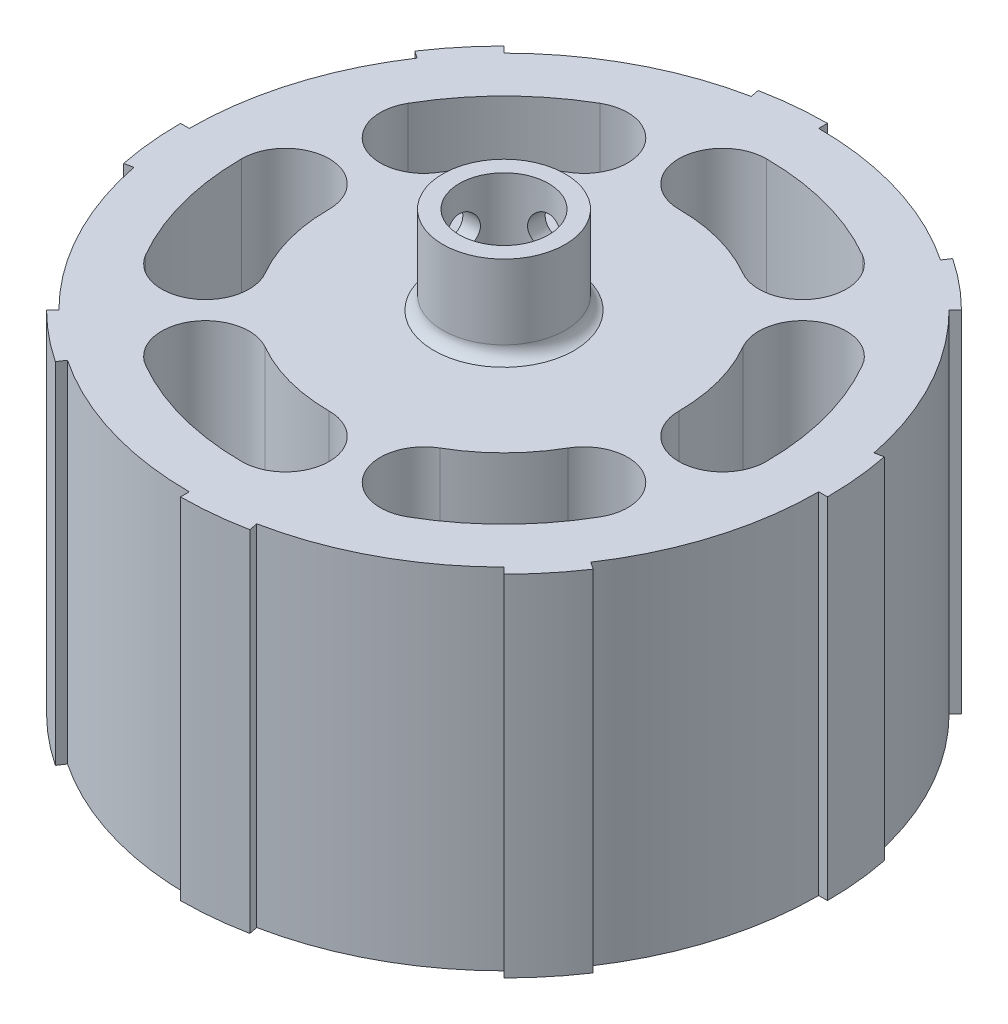
SolidWorks part; units mm, degrees
ref_plane "前视基准面" through (0, 0, 0) normal (0, 0, 1) x (1, 0, 0)
ref_plane "上视基准面" through (0, 0, 0) normal (0, 1, 0) x (1, 0, 0)
ref_plane "右视基准面" through (0, 0, 0) normal (1, 0, 0) x (0, 0, -1)
other "Configuration Table"
sketch "草图1" plane through (0, 0, 0) normal (0, 1, 0) x (1, 0, 0)
  circle A0 centre (0, 0) radius 37
  dimension "D1" = 74
extrude "凸台-拉伸1" add sketch "草图1" along normal blind 40
sketch "草图2" plane through (0, 40, 0) normal (0, 1, 0) x (1, 0, 0)
  circle A0 centre (0, 0) radius 5.1
  dimension "D1" = 10.2
extrude "切除-拉伸1" cut sketch "草图2" against normal blind 40
sketch "草图3" plane through (0, 40, 0) normal (0, 1, 0) x (1, 0, 0)
  line L0 (-1000, 0) -> (49000, 0) construction
  line L1 (0, -1000) -> (0, 49000) construction
  circle A0 centre (0, 0) radius 30
  circle A1 centre (0, 30) radius 5
  circle A3 centre (25.9808, 15) radius 5
  circle A4 centre (30, 0) radius 5
  circle A5 centre (25.9808, -15) radius 5
  circle A7 centre (0, -30) radius 5
  circle A8 centre (-15, -25.9808) radius 5
  circle A9 centre (-25.9808, -15) radius 5
  circle A11 centre (-25.9808, 15) radius 5
  circle A12 centre (-15, 25.9808) radius 5
  circle A13 centre (0, 0) radius 25
  circle A14 centre (0, 0) radius 35
  circle A15 centre (-30, 0) radius 5 [skipped]
  circle A16 centre (15, -25.9808) radius 5 [skipped]
  circle A17 centre (15, 25.9808) radius 5 [skipped]
  point P34 (0, 0)
  dimension "D1" = 60
  dimension "D2" = 10
  dimension "D3" = 12
extrude "切除-拉伸2" cut sketch "草图3" against normal blind 40 contours A0 A11 | A0 A11 | A13 A12 A0 A11 | A12 A14 A11 A0 | A0 A12 | A0 A12 | A1 A14 A12 A0 | A13 A1 A0 A12 | A0 A1 | A0 A1 | A0 A9 | A0 A9 | A9 A14 A8 A0 | A13 A9 A0 A8 | A0 A8 | A0 A8 | A8 A14 A7 A0 | A13 A8 A0 A7 | A0 A7 | A0 A7 | A0 A5 | A0 A5 | A0 A4 | A0 A4 | A0 A3 | A0 A3 | A4 A14 A3 A0 | A13 A4 A0 A3 | A13 A5 A0 A4 | A5 A14 A4 A0 region at (27.8047, 40, 0) region at (32.0453, 40, 0) region at (26.1943, 40, -7.0188) region at (31.6944, 40, -8.4925) region at (31.6944, 40, 8.4925) region at (26.1943, 40, 7.0188) region at (24.0795, 40, -13.9023) region at (27.752, 40, -16.0226) region at (27.752, 40, 16.0226) region at (24.0795, 40, 13.9023) region at (-7.0188, 40, -26.1943) region at (0, 40, -27.8047) region at (0, 40, -32.0453) region at (-8.4925, 40, -31.6944) region at (-8.4925, 40, 31.6944) region at (0, 40, 32.0453) region at (0, 40, 27.8047) region at (-7.0188, 40, 26.1943) region at (-19.1756, 40, -19.1756) region at (-13.9023, 40, -24.0795) region at (-16.0226, 40, -27.752) region at (-23.2019, 40, -23.2019) region at (-23.2019, 40, 23.2019) region at (-16.0226, 40, 27.752) region at (-13.9023, 40, 24.0795) region at (-19.1756, 40, 19.1756) region at (-24.0795, 40, -13.9023) region at (-27.752, 40, -16.0226) region at (-27.752, 40, 16.0226) region at (-24.0795, 40, 13.9023)
sketch "草图4" plane through (0, 40, 0) normal (0, 1, 0) x (1, 0, 0)
  circle A0 centre (0, 0) radius 7
  circle A1 centre (0, 0) radius 5.1
  dimension "D1" = 14
extrude "凸台-拉伸2" add sketch "草图4" along normal mid plane 20
sketch "草图5" plane through (0, 0, 0) normal (0, -1, 0) x (1, 0, 0)
  circle A0 centre (0, 0) radius 5.1
sketch "草图6" plane through (0, 0, 0) normal (0, 0, 1) x (1, 0, 0)
  line L0 (0, 50) -> (0, 45)
  line L1 (5.1, 50) -> (-5.1, 50) construction
  circle A0 centre (0, 45) radius 2
  dimension "D2" = 4
  dimension "D1" = 5
extrude "切除-拉伸3" cut sketch "草图6" against normal up to next contours A0 region at (-1.3742, 43.6258, 0)
sketch "草图7" plane through (0, 0, 0) normal (1, 0, 0) x (0, 0, -1)
  line L0 (0, 50) -> (0, 45)
  line L1 (7, 50) -> (-7, 50) construction
  circle A0 centre (0, 45) radius 2
  dimension "D2" = 4
  dimension "D1" = 5
extrude "切除-拉伸4" cut sketch "草图7" against normal up to next contours A0 region at (0, 43.6258, 1.3742)
sketch "草图10" plane through (0, 0, 0) normal (0, -1, 0) x (1, 0, 0)
  line L0 (0, 0) -> (0, 37)
  line L1 (0, 0) -> (7.2183, 36.2891)
  line L2 (0, 0) -> (14.1593, 34.1835)
  line L3 (0, 0) -> (20.5561, 30.7644)
  line L4 (0, 0) -> (26.163, 26.163)
  line L5 (0, 0) -> (30.7644, 20.5561)
  line L6 (0, 0) -> (34.1835, 14.1593)
  line L7 (0, 0) -> (36.2891, 7.2183)
  line L8 (0, 0) -> (37, 0)
  line L9 (0, 0) -> (36.2891, -7.2183)
  line L10 (0, 0) -> (34.1835, -14.1593)
  line L11 (0, 0) -> (30.7644, -20.5561)
  line L12 (0, 0) -> (26.163, -26.163)
  line L13 (0, 0) -> (20.5561, -30.7644)
  line L14 (0, 0) -> (14.1593, -34.1835)
  line L15 (0, 0) -> (7.2183, -36.2891)
  line L16 (0, 0) -> (0, -37)
  line L17 (0, 0) -> (-7.2183, -36.2891)
  line L18 (0, 0) -> (-14.1593, -34.1835)
  line L19 (0, 0) -> (-20.5561, -30.7644)
  line L20 (0, 0) -> (-26.163, -26.163)
  line L21 (0, 0) -> (-30.7644, -20.5561)
  line L22 (0, 0) -> (-34.1835, -14.1593)
  line L23 (0, 0) -> (-36.2891, -7.2183)
  line L24 (0, 0) -> (-37, 0)
  line L25 (0, 0) -> (-36.2891, 7.2183)
  line L26 (0, 0) -> (-34.1835, 14.1593)
  line L27 (0, 0) -> (-30.7644, 20.5561)
  line L28 (0, 0) -> (-26.163, 26.163)
  line L29 (0, 0) -> (-20.5561, 30.7644)
  line L30 (0, 0) -> (-14.1593, 34.1835)
  line L31 (0, 0) -> (-7.2183, 36.2891)
  circle A0 centre (0, 0) radius 37
  circle A1 centre (0, 0) radius 36
  point P38 (0, 0)
  circle M14 centre (0, 0) radius 37
  dimension "D1" = 72
  dimension "D2" = 37
  dimension "D3" = 32
extrude "切除-拉伸7" cut sketch "草图10" against normal up to next contours A1 L26 L25 M14 | A1 L27 L26 M14 | A1 L28 L27 M14 | A1 L30 L29 M14 | A1 L31 L30 M14 | A1 L0 L31 M14 | A1 L2 L1 M14 | A1 L3 L2 M14 | A1 L4 L3 M14 | A1 L6 L5 M14 | A1 L7 L6 M14 | A1 L8 L7 M14 | A1 L10 L9 M14 | A1 L11 L10 M14 | A1 L12 L11 M14 | A1 L14 L13 M14 | A1 L15 L14 M14 | A1 L16 L15 M14 | A1 L18 L17 M14 | A1 L19 L18 M14 | A1 L20 L19 M14 | A1 L22 L21 M14 | A1 L23 L22 M14 | A1 L24 L23 M14 region at (-3.5721, 0, 36.2682) region at (10.579, 0, 34.8744) region at (17.1794, 0, 32.1405) region at (23.1196, 0, 28.1713) region at (32.1405, 0, 17.1794) region at (34.8744, 0, 10.579) region at (36.2682, 0, 3.5721) region at (34.8744, 0, -10.579) region at (32.1405, 0, -17.1794) region at (28.1713, 0, -23.1196) region at (17.1794, 0, -32.1405) region at (10.579, 0, -34.8744) region at (3.5721, 0, -36.2682) region at (-10.579, 0, -34.8744) region at (-17.1794, 0, -32.1405) region at (-23.1196, 0, -28.1713) region at (-32.1405, 0, -17.1794) region at (-34.8744, 0, -10.579) region at (-36.2682, 0, -3.5721) region at (-34.8744, 0, 10.579) region at (-32.1405, 0, 17.1794) region at (-28.1713, 0, 23.1196) region at (-17.1794, 0, 32.1405) region at (-10.579, 0, 34.8744)
sketch "草图14" plane through (0, 40, 0) normal (0, 1, 0) x (1, 0, 0)
  circle A0 centre (0, 0) radius 36
extrude "凸台-拉伸4" add sketch "草图14" against normal blind 40
sketch "草图15" plane through (0, 40, 0) normal (0, 1, 0) x (1, 0, 0)
  circle A0 centre (0, 0) radius 25
  circle A1 centre (0, 25) radius 5
  circle A2 centre (12.5, 21.6506) radius 5
  circle A3 centre (21.6506, 12.5) radius 5
  circle A4 centre (25, 0) radius 5
  circle A5 centre (21.6506, -12.5) radius 5
  circle A6 centre (12.5, -21.6506) radius 5
  circle A7 centre (0, -25) radius 5
  circle A8 centre (-12.5, -21.6506) radius 5
  circle A9 centre (-21.6506, -12.5) radius 5
  circle A10 centre (-25, 0) radius 5
  circle A11 centre (-21.6506, 12.5) radius 5
  circle A12 centre (-12.5, 21.6506) radius 5
  circle A13 centre (0, 0) radius 30
  circle A14 centre (0, 0) radius 20
  point P30 (0, 0)
  dimension "D1" = 50
  dimension "D2" = 10
  dimension "D3" = 12
extrude "切除-拉伸11" cut sketch "草图15" against normal blind 40 contours A14 A12 A0 A11 | A12 A13 A11 A0 | A0 A11 | A0 A11 | A0 A12 | A0 A12 | A0 A1 | A0 A1 | A2 A13 A1 A0 | A14 A2 A0 A1 | A0 A2 | A0 A2 | A0 A3 | A0 A3 | A14 A4 A0 A3 | A4 A13 A3 A0 | A0 A4 | A0 A4 | A0 A5 | A0 A5 | A0 A6 | A0 A6 | A14 A6 A0 A5 | A6 A13 A5 A0 | A0 A7 | A0 A7 | A0 A8 | A0 A8 | A8 A13 A7 A0 | A14 A8 A0 A7 | A0 A9 | A0 A9 | A14 A10 A0 A9 | A10 A13 A9 A0 | A0 A10 | A0 A10 region at (22.7904, 40, 0) region at (27.0295, 40, 0) region at (21.2179, 40, -5.6853) region at (27.0803, 40, -7.2562) region at (19.7371, 40, -11.3952) region at (23.4082, 40, -13.5147) region at (23.4082, 40, 13.5147) region at (19.7371, 40, 11.3952) region at (19.8242, 40, 19.8242) region at (15.5326, 40, 15.5326) region at (11.3952, 40, -19.7371) region at (13.5147, 40, -23.4082) region at (5.6853, 40, -21.2179) region at (7.2562, 40, -27.0803) region at (13.5147, 40, 23.4082) region at (11.3952, 40, 19.7371) region at (0, 40, -22.7904) region at (0, 40, -27.0295) region at (-7.2562, 40, 27.0803) region at (0, 40, 27.0295) region at (0, 40, 22.7904) region at (-5.6853, 40, 21.2179) region at (-15.5326, 40, -15.5326) region at (-11.3952, 40, -19.7371) region at (-13.5147, 40, -23.4082) region at (-19.8242, 40, -19.8242) region at (-13.5147, 40, 23.4082) region at (-11.3952, 40, 19.7371) region at (-19.7371, 40, -11.3952) region at (-23.4082, 40, -13.5147) region at (-27.0803, 40, 7.2562) region at (-23.4082, 40, 13.5147) region at (-19.7371, 40, 11.3952) region at (-21.2179, 40, 5.6853) region at (-22.7904, 40, 0) region at (-27.0295, 40, 0)
sketch "草图17" plane through (0, 40, 0) normal (0, 1, 0) x (1, 0, 0)
  circle A0 centre (0, 0) radius 5.1
extrude "切除-拉伸12" cut sketch "草图17" against normal blind 40
ref_plane "基准面2" through (0, 20, 0) normal (0, 1, 0) x (1, 0, 0)
sketch "草图18" plane through (0, 20, 0) normal (0, 1, 0) x (1, 0, 0)
  line L0 (-27.5, 0) -> (27.5, 0) construction
  circle A0 centre (0, 0) radius 37
  circle A1 centre (0, 0) radius 10
  dimension "D1" = 20
sketch "草图20" plane through (0, 0, 0) normal (0, 0, 1) x (1, 0, 0)
  line L0 (-7, 40) -> (-7, 41.5)
  line L2 (-7, 43.0001) -> (-7, 40) construction
  line L3 (0, 40) -> (-20.0005, 40) construction
  line L4 (-8.0182, 40) -> (-7, 40)
  line L5 (0, -950) -> (0, 49050) construction
  line L6 (7, 50) -> (-7, 50) construction
  arc A0 (-7, 41.5) -> (-8.0182, 40) centre (-8.6141, 41.5) cw
  point P14 (0, 50)
revolve "旋转1" add sketch "草图20" angle 360 about L5
